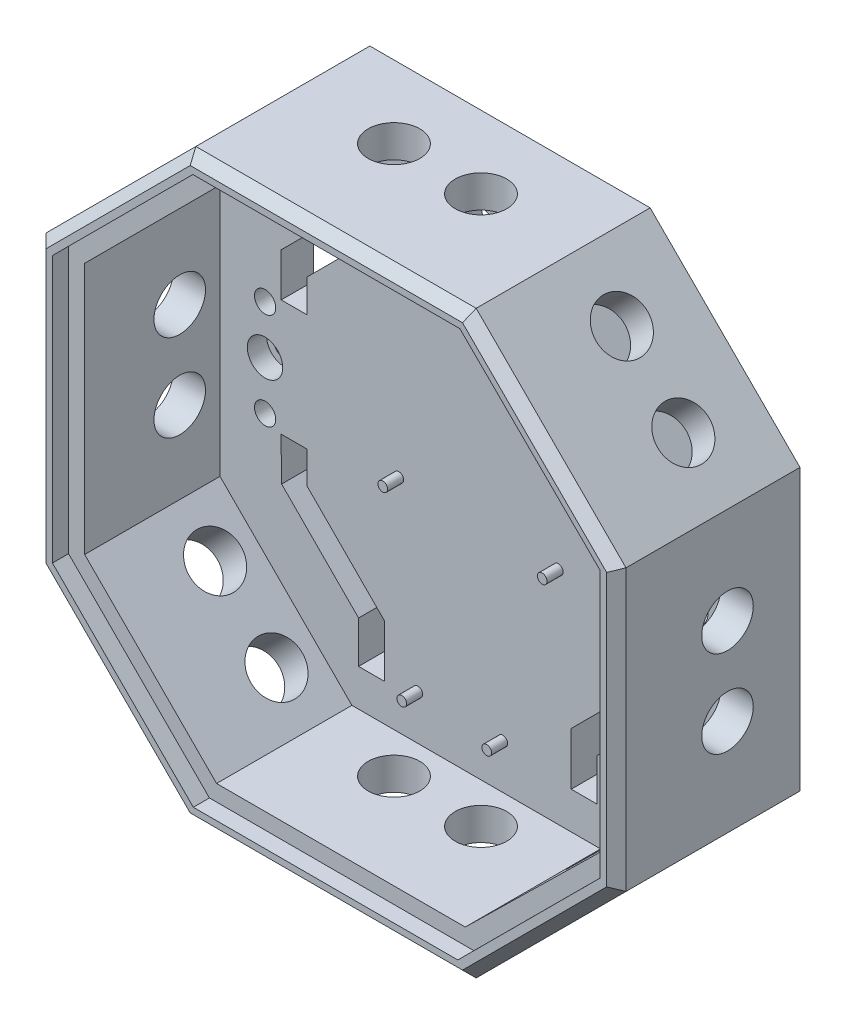
SolidWorks part; units mm, degrees
other "Marcação1"
sketch "Esboço43" plane through (-89.9485, 90.0021, 50) normal (-0.1614, 0.9573, 0.24) x (-0.9837, -0.1366, -0.1167)
ref_plane "Plano frontal" through (0, 0, 0) normal (0, 0, 1) x (1, 0, 0)
ref_plane "Plano superior" through (0, 0, 0) normal (0, 1, 0) x (1, 0, 0)
ref_plane "Plano direito" through (0, 0, 0) normal (1, 0, 0) x (0, 0, -1)
sketch "Esboço12" plane through (0, 0, 0) normal (0, 0, 1) x (1, 0, 0)
  line L0 (-43.442, 89.9928) -> (43.5474, 89.9928)
  line L1 (43.5474, 89.9928) -> (90.0515, 43.4886)
  line L2 (90.0515, 43.4886) -> (90.0515, -43.503)
  line L3 (90.0515, -43.503) -> (43.5473, -90.0072)
  line L4 (43.5473, -90.0072) -> (-43.4421, -90.0072)
  line L5 (-43.4421, -90.0072) -> (-89.9485, -43.5007)
  line L6 (-89.9485, -43.5007) -> (-89.9485, 43.4865)
  line L7 (-89.9485, 43.4865) -> (-43.442, 89.9928)
  line L8 (-60.9485, 31.4742) -> (-31.4298, 60.9928)
  line L9 (-31.4298, 60.9928) -> (-17.9498, 60.9928)
  line L10 (-17.9498, 60.9928) -> (-17.9498, 52.9928)
  line L11 (-17.9498, 52.9928) -> (-28.1149, 52.9928)
  line L12 (-28.1149, 52.9928) -> (-52.9485, 28.1593)
  line L13 (-52.9485, 28.1593) -> (-52.9485, 17.9942)
  line L14 (-52.9485, 17.9942) -> (-60.9485, 17.9942)
  line L15 (-60.9485, 17.9942) -> (-60.9485, 31.4742)
  line L64 (53.0515, 17.9922) -> (53.0515, 28.1572)
  line L65 (61.0515, 17.9922) -> (53.0515, 17.9922)
  line L68 (53.0515, 28.1572) -> (28.2179, 52.9908)
  line L69 (28.2179, 52.9908) -> (18.0502, 52.9908)
  line L70 (18.0502, 52.9908) -> (18.0502, 60.9943)
  line L71 (18.0502, 60.9943) -> (31.5302, 61.0059)
  line L78 (53.1319, -18.091) -> (61.1319, -18.091)
  line L79 (61.1319, -18.091) -> (61.1047, -31.4376)
  line L80 (-52.9485, -18.091) -> (-52.9485, -28.0175)
  line L81 (-61.0225, -18.0924) -> (-52.9485, -18.091)
  line L82 (-60.8258, -31.4376) -> (-61.0225, -18.0924)
  line L93 (-36.9485, -58.3372) -> (-36.9485, -68.5072)
  line L94 (-36.9485, -68.5072) -> (-28.9485, -68.5072)
  line L100 (-28.9485, -68.5072) -> (-28.9485, -55.0272)
  line L105 (29.0515, -68.5072) -> (29.0515, -55.0272)
  line L106 (29.0515, -68.5072) -> (37.0515, -68.5072)
  line L107 (37.0515, -68.5072) -> (37.0515, -58.3376)
  line L110 (31.5302, 61.0059) -> (61.0515, 31.4846)
  line L111 (61.0515, 31.4846) -> (61.0515, 17.9922)
  line L115 (-60.8258, -31.4376) -> (-36.9485, -55.4908)
  line L116 (-36.9485, -55.4908) -> (-36.9485, -58.3372)
  line L118 (-52.9485, -28.0175) -> (-28.9485, -52.1942)
  line L119 (-28.9485, -52.1942) -> (-28.9485, -55.0272)
  line L120 (61.1047, -31.4376) -> (37.0515, -55.4908)
  line L121 (37.0515, -58.3376) -> (37.0515, -55.4908)
  line L122 (53.1319, -18.091) -> (53.1319, -28.0967)
  line L123 (53.1319, -28.0967) -> (29.0515, -52.177)
  line L124 (29.0515, -52.177) -> (29.0515, -55.0272)
  circle A3 centre (66.0515, 14.9928) radius 3.3
  circle A4 centre (66.0515, -15.0072) radius 3.3
  circle A5 centre (-65.9485, 14.9928) radius 3.3
  circle A6 centre (-65.9485, -15.0072) radius 3.3
  circle A7 centre (0.0515, 64.9928) radius 9
  point P9 (-52.9485, -23.0543)
  point P47 (0.0515, -0.0092)
  point P56 (0.0011, 0)
  point P57 (33.0515, -68.5072)
  point P58 (0.0006, -0.0006)
  dimension "D8" = 8
  dimension "D16" = 24
  dimension "D17" = 30
  dimension "D18" = 36
  dimension "D19" = 75
  dimension "D20" = 29
  dimension "D21" = 6.6
  dimension "D22" = 6.6
  dimension "D23" = 24
  dimension "D24" = 13.48
  dimension "D25" = 13.48
  dimension "D26" = 18
  dimension "D30" = 30
  dimension "D38" = 8
  dimension "D11" = 24
  dimension "D32" = 90
  dimension "D34" = 29
  dimension "D39" = 8
  dimension "D43" = 6.6
  dimension "D44" = 6.6
  dimension "D1" = 180
  dimension "D2" = 180
  dimension "D3" = 188.79
  dimension "D4" = 188.79
  dimension "D5" = 65.77
  dimension "D6" = 65.7669
  dimension "D7" = 65.77
  dimension "D9" = 10.17
  dimension "D10" = 29
  dimension "D12" = 8
  dimension "D13" = 8
  dimension "D14" = 35.12
  dimension "D15" = 13.48
  dimension "D27" = 13.48
  dimension "D28" = 25
  dimension "D29" = 24
  dimension "D31" = 61
  dimension "D33" = 8
  dimension "D35" = 8
  dimension "D36" = 61
  dimension "D37" = 8
  dimension "D40" = 8
  dimension "D41" = 21.5
  dimension "D42" = 21.5
extrude "Ressalto-extrusão4" add sketch "Esboço12" along normal blind 10
sketch "Esboço16" plane through (0, 0, 10) normal (0, 0, 1) x (1, 0, 0)
  line L4 (90.0515, -43.503) -> (90.0515, 43.4886) construction
  line L9 (80.0515, 38.2235) -> (80.0515, -38.9298)
  line L10 (80.0515, -38.9298) -> (38.1534, -80.0072)
  line L11 (38.1534, -80.0072) -> (-39.0147, -80.0072)
  line L12 (80.0515, 38.2235) -> (80.0515, 39.3546)
  line L13 (-89.9485, -43.5007) -> (-89.9485, 43.4865)
  line L14 (-89.9485, 43.4865) -> (-43.442, 89.9928)
  line L15 (-43.442, 89.9928) -> (43.5474, 89.9928)
  line L16 (43.5474, 89.9928) -> (90.0515, 43.4886)
  line L17 (90.0515, 43.4886) -> (90.0515, -43.503)
  line L18 (90.0515, -43.503) -> (43.5473, -90.0072)
  line L19 (43.5473, -90.0072) -> (-43.4421, -90.0072)
  line L20 (-89.9485, -43.5007) -> (-43.4421, -90.0072) construction
  line L21 (-43.4421, -90.0072) -> (43.5473, -90.0072) construction
  line L22 (-43.4421, -90.0072) -> (-89.9485, -43.5007)
  line L25 (39.4133, 79.9928) -> (80.0515, 39.3546)
  line L26 (61.0515, 31.4846) -> (31.5302, 61.0059) construction
  line L27 (-79.9485, -38.9298) -> (-39.0147, -80.0072)
  line L29 (-39.2999, 79.9928) -> (39.4133, 79.9928)
  line L35 (-79.9433, 39.3495) -> (-39.2999, 79.9928)
  line L36 (-31.4298, 60.9928) -> (-60.9485, 31.4742) construction
  line L37 (-79.9433, 39.3495) -> (-79.9485, -38.9298)
  dimension "D1" = 19
  dimension "D3" = 10
  dimension "D4" = 19
  dimension "D5" = 10
  dimension "D6" = 10
extrude "Ressalto-extrusão5" add sketch "Esboço16" along normal blind 47
sketch "Esboço17" plane through (0, -90.0072, 0) normal (0, -1, 0) x (-1, 0, 0)
  line L0 (43.4421, 0) -> (-43.5473, 0) construction
  line L1 (43.4421, -57) -> (43.4421, 0) construction
  circle A0 centre (13.4521, -22.5) radius 8
  circle A1 centre (-13.5479, -22.5) radius 8
  dimension "D1" = 22.5
  dimension "D2" = 22.5
  dimension "D3" = 27
  dimension "D4" = 29.99
extrude "Corte-extrusão2" cut sketch "Esboço17" against normal blind 210
sketch "Esboço18" plane through (66.7772, -66.7773, 0) normal (0.7071, -0.7071, 0) x (0, 0, -1)
  line L0 (-57, 32.9149) -> (0, 32.9149) construction
  line L2 (0, -32.852) -> (0, 32.9149) construction
  circle A0 centre (-22.5, 13.5249) radius 8
  circle A1 centre (-22.5, -13.4751) radius 8
  dimension "D1" = 27
  dimension "D4" = 22.5
  dimension "D2" = 19.39
  dimension "D3" = 22.5
extrude "Corte-extrusão3" cut sketch "Esboço18" against normal blind 210
sketch "Esboço19" plane through (-66.7247, -66.7246, 0) normal (-0.7071, -0.7071, 0) x (0.7071, -0.7071, 0)
  line L0 (-32.8434, 0) -> (32.9266, 0) construction
  line L1 (-32.8434, 57) -> (-32.8434, 0) construction
  circle A0 centre (-13.4534, 22.5) radius 8
  circle A1 centre (13.5466, 22.5) radius 8
  dimension "D1" = 22.5
  dimension "D2" = 27
  dimension "D3" = 19.39
extrude "Corte-extrusão4" cut sketch "Esboço19" against normal blind 210
sketch "Esboço20" plane through (90.0515, 0, 0) normal (1, 0, 0) x (0, 0, -1)
  line L0 (-57, 43.4886) -> (0, 43.4886) construction
  line L1 (0, -43.503) -> (0, 43.4886) construction
  circle A0 centre (-22.5, 13.4986) radius 8
  circle A1 centre (-22.5, -13.5014) radius 8
  dimension "D1" = 27
  dimension "D2" = 29.99
  dimension "D4" = 22.5
  dimension "D3" = 22.5
extrude "Corte-extrusão5" cut sketch "Esboço20" against normal blind 210
sketch "Esboço25" plane through (0, 0, 0) normal (0, 0, -1) x (-1, 0, 0)
  line L0 (-76.0515, 9.9928) -> (-56.0515, 9.9928)
  line L1 (-56.0515, 9.9928) -> (-56.0515, -10.0072)
  line L2 (-56.0515, -10.0072) -> (-76.0515, -10.0072)
  line L3 (-76.0515, -10.0072) -> (-76.0515, 9.9928)
  line L4 (55.9485, 9.9928) -> (75.9485, 9.9928)
  line L5 (75.9485, 9.9928) -> (75.9485, -10.0072)
  line L6 (75.9485, -10.0072) -> (55.9485, -10.0072)
  line L7 (55.9485, -10.0072) -> (55.9485, 9.9928)
  line L8 (-90.0515, -43.503) -> (-90.0515, 43.4886) construction
  line L9 (89.9485, 43.4865) -> (89.9485, -43.5007) construction
  line L10 (43.4421, -90.0072) -> (-43.5473, -90.0072) construction
  circle A0 centre (65.9485, 14.9928) radius 3.3 construction
  dimension "D2" = 5
  dimension "D3" = 14
  dimension "D1" = 20
  dimension "D4" = 20
  dimension "D5" = 14
  dimension "D6" = 20
  dimension "D7" = 80
  dimension "D8" = 80
sketch "Esboço31" plane through (0, 0, 10) normal (0, 0, 1) x (1, 0, 0)
  line L8 (-52.9485, -28.0175) -> (-52.9485, -18.091) construction
  line L9 (-28.9485, -68.5072) -> (-28.9485, -52.1942) construction
  line L10 (-20.6965, -68.1065) -> (9.6801, -68.1065) construction
  line L11 (-39.0147, -80.0072) -> (38.1534, -80.0072) construction
  line L14 (29.0515, -68.5072) -> (37.0515, -68.5072) construction
  circle A0 centre (-24.4485, -11.4072) radius 1.5
  circle A1 centre (25.0515, -11.4072) radius 1.5
  circle A2 centre (-18.5485, -66.1065) radius 1.5
  circle A3 centre (7.8315, -66.1072) radius 1.4983
  dimension "D6" = 28.5
  dimension "D8" = 2
  dimension "D1" = 49.5
  dimension "D2" = 26.38
  dimension "D3" = 10.4
  dimension "D4" = 13.9
  dimension "D5" = 57.1
sketch "Esboço34" plane through (0, 0, 10) normal (0, 0, 1) x (1, 0, 0)
  circle A0 centre (-65.9827, 0) radius 3
  circle A1 centre (66.0214, 0) radius 3
  dimension "D1" = 6
  dimension "D2" = 6
extrude "Corte-extrusão6" cut sketch "Esboço34" against normal blind 10
extrude "Ressalto-extrusão6" add sketch "Esboço31" along normal blind 5
sketch "Esboço62" plane through (0, 0, 57) normal (0, 0, 1) x (1, 0, 0)
  line L2 (39.4133, 79.9928) -> (80.0515, 39.3546)
  line L3 (80.0515, 39.3546) -> (80.0515, -38.9298)
  line L4 (80.0515, -38.9298) -> (38.1534, -80.0072)
  line L5 (38.1534, -80.0072) -> (-39.0147, -80.0072)
  line L10 (-84.9485, 41.4206) -> (-41.3759, 84.9879)
  line L12 (-84.9485, 41.4206) -> (-84.9485, -41.2153)
  line L13 (-84.9485, -41.2153) -> (-41.2284, -85.0072)
  line L14 (-79.9433, 39.3495) -> (-39.2999, 79.9928)
  line L15 (-39.2999, 79.9928) -> (39.4133, 79.9928)
  line L16 (-41.2284, -85.0072) -> (40.8504, -85.0072)
  line L17 (40.8504, -85.0072) -> (85.0515, -40.8785)
  line L19 (-79.9485, -38.9298) -> (-39.0147, -80.0072)
  line L21 (-79.9433, 39.3495) -> (-79.9485, -38.9298)
  line L22 (-41.3759, 84.9879) -> (41.4803, 84.9928)
  line L23 (41.4803, 84.9928) -> (85.0515, 41.7589)
  line L26 (85.0515, 41.7589) -> (85.0515, -40.8785)
  line L27 (90.0515, -43.503) -> (90.0515, 43.4886) construction
  dimension "D1" = 5
  dimension "D2" = 170
extrude "Corte-extrusão26" cut sketch "Esboço62" against normal blind 5
fillet "Chanfro1" radius 3 8 edges at (-66.6952, 66.7396, 57) (-89.9485, -0.0071, 57) (-66.6953, -66.7539, 57) (0.0526, -90.0072, 57) (66.7994, -66.7551, 57) (90.0515, -0.0072, 57) (66.7994, 66.7407, 57) (0.0527, 89.9928, 57) type face fillet profile chamfer first side face at (-89.9485, 13.4986, 14.5) first side face at (-70.5889, 62.846, 22.5) first side face at (-13.4521, 89.9928, 14.5) first side face at (82.0058, 51.5343, 22.5) first side face at (90.0515, 13.4986, 14.5) first side face at (62.9057, -70.6488, 22.5) first side face at (-13.4521, -90.0072, 14.5) first side face at (-51.489, -81.9603, 22.5) second side face at (-0.0084, 0.1315, 57)
hole_wizard "Rebaixo para SHCS M61" positions "3DSketch1" profile "Esboço63" counterbore size "M6" standard "Ansi Metric" end condition through all
sketch3d "3DSketch1"
  line L0 (-65.9827, 0, 0) -> (-65.9827, 0, 10) construction
  point P0 (-65.9827, 0, 10)
sketch "Esboço63" plane through (-65.9827, 0, 10) normal (1, 0, 0) x (0, -1, 0)
  line L0 (0, 0) -> (0, 10)
  line L1 (0, 10) -> (3.3, 10)
  line L3 (3.3, 10) -> (3.3, 6)
  line L4 (3.3, 6) -> (5.5, 6)
  line L5 (5.5, 6) -> (5.5, 0)
  line L7 (5.5, 0) -> (0, 0)
  line L11 (0, -6.35) -> (0, 107.95) construction
  dimension "Thru Hole Dia." = 6.6
  dimension "Thru Hole Depth" = 10
  dimension "C'Bore Dia." = 11
  dimension "C'Bore Depth" = 6
hole_wizard "Rebaixo para SHCS M62" positions "3DSketch2" profile "Esboço64" counterbore size "M6" standard "Ansi Metric" end condition through all
sketch3d "3DSketch2"
  line L0 (66.0214, 0, 0) -> (66.0214, 0, 10) construction
  point P0 (66.0214, 0, 10)
sketch "Esboço64" plane through (66.0214, 0, 10) normal (1, 0, 0) x (0, -1, 0)
  line L0 (0, 0) -> (0, 10)
  line L1 (0, 10) -> (3.3, 10)
  line L3 (3.3, 10) -> (3.3, 6)
  line L4 (3.3, 6) -> (5.5, 6)
  line L5 (5.5, 6) -> (5.5, 0)
  line L7 (5.5, 0) -> (0, 0)
  line L11 (0, -6.35) -> (0, 107.95) construction
  dimension "Thru Hole Dia." = 6.6
  dimension "Thru Hole Depth" = 10
  dimension "C'Bore Dia." = 11
  dimension "C'Bore Depth" = 6
